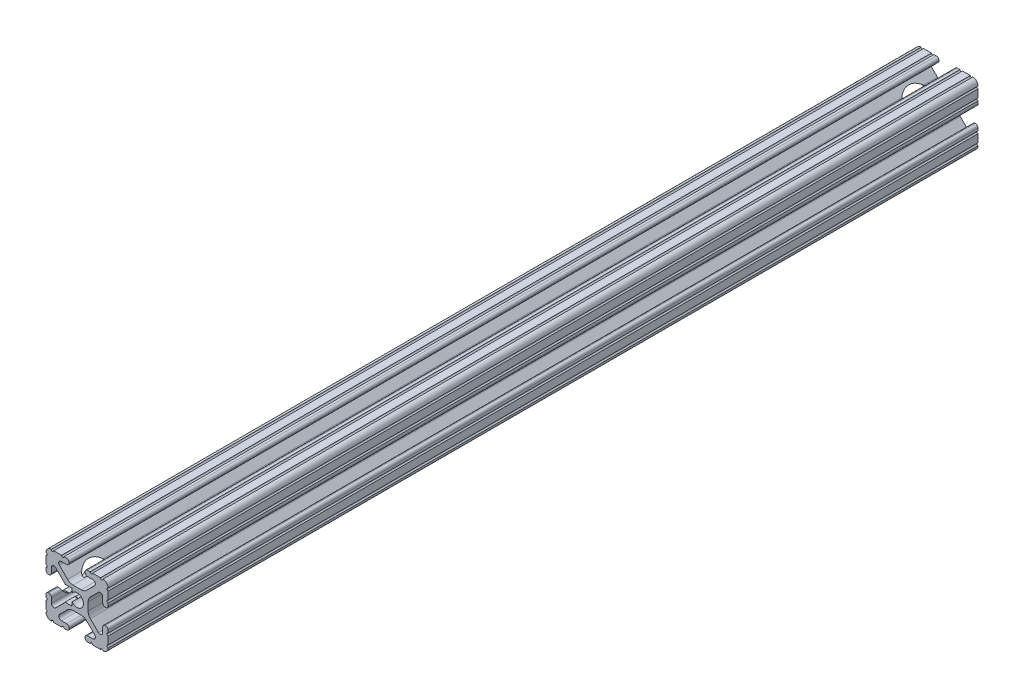
SolidWorks part; units mm, degrees
ref_plane "Front Plane" through (0, 0, 0) normal (0, 0, 1) x (1, 0, 0)
ref_plane "Top Plane" through (0, 0, 0) normal (0, 1, 0) x (1, 0, 0)
ref_plane "Right Plane" through (0, 0, 0) normal (1, 0, 0) x (0, 0, -1)
sketch "Sketch1" plane through (0, 0, 0) normal (0, 0, 1) x (1, 0, 0)
  line L88 (-7.1797, -8.6452) -> (-3.9523, -5.4237)
  line L89 (-1.7093, -4.4958) -> (1.7093, -4.4958)
  line L90 (3.9523, -5.4237) -> (7.1797, -8.6452)
  line L91 (6.4164, -10.4902) -> (4.2875, -10.4902)
  line L92 (3.2385, -11.5392) -> (3.2385, -11.651)
  line L93 (4.2875, -12.7) -> (5.3171, -12.7)
  line L94 (6.3331, -12.7) -> (9.5504, -12.7)
  line L95 (12.7, -9.5504) -> (12.7, -6.3331)
  line L96 (12.7, -5.3171) -> (12.7, -4.2875)
  line L97 (11.651, -3.2385) -> (11.5392, -3.2385)
  line L98 (10.4902, -4.2875) -> (10.4902, -6.4021)
  line L99 (8.7371, -7.1294) -> (5.441, -3.8408)
  line L100 (4.5085, -1.5932) -> (4.5085, 1.5932)
  line L101 (5.441, 3.8408) -> (8.7371, 7.1294)
  line L102 (10.4902, 6.4021) -> (10.4902, 4.2875)
  line L103 (11.5392, 3.2385) -> (11.651, 3.2385)
  line L104 (12.7, 4.2875) -> (12.7, 5.3171)
  line L105 (12.7, 6.3331) -> (12.7, 9.5504)
  line L106 (9.5504, 12.7) -> (6.3331, 12.7)
  line L107 (5.3171, 12.7) -> (4.2875, 12.7)
  line L108 (3.2385, 11.651) -> (3.2385, 11.5392)
  line L109 (4.2875, 10.4902) -> (6.4768, 10.4902)
  line L110 (7.207, 8.7244) -> (3.8983, 5.4232)
  line L111 (1.6558, 4.4958) -> (-1.6558, 4.4958)
  line L112 (-3.8983, 5.4232) -> (-7.207, 8.7244)
  line L113 (-6.4768, 10.4902) -> (-4.2875, 10.4902)
  line L114 (-3.2385, 11.5392) -> (-3.2385, 11.651)
  line L115 (-4.2875, 12.7) -> (-5.3171, 12.7)
  line L116 (-6.3331, 12.7) -> (-9.5504, 12.7)
  line L117 (-12.7, 9.5504) -> (-12.7, 6.3331)
  line L118 (-12.7, 5.3171) -> (-12.7, 4.2875)
  line L119 (-11.651, 3.2385) -> (-11.5392, 3.2385)
  line L120 (-10.4902, 4.2875) -> (-10.4902, 6.4021)
  line L121 (-8.7371, 7.1294) -> (-5.441, 3.8408)
  line L122 (-4.5085, 1.5932) -> (-4.5085, -1.5932)
  line L123 (-5.441, -3.8408) -> (-8.7371, -7.1294)
  line L124 (-10.4902, -6.4021) -> (-10.4902, -4.2875)
  line L125 (-11.5392, -3.2385) -> (-11.651, -3.2385)
  line L126 (-12.7, -4.2875) -> (-12.7, -5.3171)
  line L127 (-12.7, -6.3331) -> (-12.7, -9.5504)
  line L128 (-9.5504, -12.7) -> (-6.3331, -12.7)
  line L129 (-5.3171, -12.7) -> (-4.2875, -12.7)
  line L130 (-3.2385, -11.651) -> (-3.2385, -11.5392)
  line L131 (-4.2875, -10.4902) -> (-6.4164, -10.4902)
  circle A1 centre (0, 0) radius 2.6035
  arc A104 (-7.1797, -8.6452) -> (-6.4164, -10.4902) centre (-6.4164, -9.4098) ccw
  arc A105 (-1.7093, -4.4958) -> (-3.9523, -5.4237) centre (-1.7093, -7.6708) ccw
  arc A106 (3.9523, -5.4237) -> (1.7093, -4.4958) centre (1.7093, -7.6708) ccw
  arc A107 (6.4164, -10.4902) -> (7.1797, -8.6452) centre (6.4164, -9.4098) ccw
  arc A108 (4.2875, -10.4902) -> (3.2385, -11.5392) centre (4.2875, -11.5392) ccw
  arc A109 (3.2385, -11.651) -> (4.2875, -12.7) centre (4.2875, -11.651) ccw
  arc A110 (6.3331, -12.7) -> (5.3171, -12.7) centre (5.8251, -12.7) ccw
  arc A111 (10.5664, -12.6998) -> (9.5504, -12.7) centre (10.0584, -12.7) ccw
  arc A112 (10.5664, -12.6998) -> (12.6998, -10.5664) centre (10.5918, -10.5918) ccw
  arc A113 (12.7, -9.5504) -> (12.6998, -10.5664) centre (12.7, -10.0584) ccw
  arc A114 (12.7, -5.3171) -> (12.7, -6.3331) centre (12.7, -5.8251) ccw
  arc A115 (12.7, -4.2875) -> (11.651, -3.2385) centre (11.651, -4.2875) ccw
  arc A116 (11.5392, -3.2385) -> (10.4902, -4.2875) centre (11.5392, -4.2875) ccw
  arc A117 (8.7371, -7.1294) -> (10.4902, -6.4021) centre (9.4628, -6.4021) ccw
  arc A118 (4.5085, -1.5932) -> (5.441, -3.8408) centre (7.6835, -1.5932) ccw
  arc A119 (5.441, 3.8408) -> (4.5085, 1.5932) centre (7.6835, 1.5932) ccw
  arc A120 (10.4902, 6.4021) -> (8.7371, 7.1294) centre (9.4628, 6.4021) ccw
  arc A121 (10.4902, 4.2875) -> (11.5392, 3.2385) centre (11.5392, 4.2875) ccw
  arc A122 (11.651, 3.2385) -> (12.7, 4.2875) centre (11.651, 4.2875) ccw
  arc A123 (12.7, 6.3331) -> (12.7, 5.3171) centre (12.7, 5.8251) ccw
  arc A124 (12.6998, 10.5664) -> (12.7, 9.5504) centre (12.7, 10.0584) ccw
  arc A125 (12.6998, 10.5664) -> (10.5664, 12.6998) centre (10.5918, 10.5918) ccw
  arc A126 (9.5504, 12.7) -> (10.5664, 12.6998) centre (10.0584, 12.7) ccw
  arc A127 (5.3171, 12.7) -> (6.3331, 12.7) centre (5.8251, 12.7) ccw
  arc A128 (4.2875, 12.7) -> (3.2385, 11.651) centre (4.2875, 11.651) ccw
  arc A129 (3.2385, 11.5392) -> (4.2875, 10.4902) centre (4.2875, 11.5392) ccw
  arc A130 (7.207, 8.7244) -> (6.4768, 10.4902) centre (6.4768, 9.4563) ccw
  arc A131 (1.6558, 4.4958) -> (3.8983, 5.4232) centre (1.6558, 7.6708) ccw
  arc A132 (-3.8983, 5.4232) -> (-1.6558, 4.4958) centre (-1.6558, 7.6708) ccw
  arc A133 (-6.4768, 10.4902) -> (-7.207, 8.7244) centre (-6.4768, 9.4563) ccw
  arc A134 (-4.2875, 10.4902) -> (-3.2385, 11.5392) centre (-4.2875, 11.5392) ccw
  arc A135 (-3.2385, 11.651) -> (-4.2875, 12.7) centre (-4.2875, 11.651) ccw
  arc A136 (-6.3331, 12.7) -> (-5.3171, 12.7) centre (-5.8251, 12.7) ccw
  arc A137 (-10.5664, 12.6998) -> (-9.5504, 12.7) centre (-10.0584, 12.7) ccw
  arc A138 (-10.5664, 12.6998) -> (-12.6998, 10.5664) centre (-10.5918, 10.5918) ccw
  arc A139 (-12.7, 9.5504) -> (-12.6998, 10.5664) centre (-12.7, 10.0584) ccw
  arc A140 (-12.7, 5.3171) -> (-12.7, 6.3331) centre (-12.7, 5.8251) ccw
  arc A141 (-12.7, 4.2875) -> (-11.651, 3.2385) centre (-11.651, 4.2875) ccw
  arc A142 (-11.5392, 3.2385) -> (-10.4902, 4.2875) centre (-11.5392, 4.2875) ccw
  arc A143 (-8.7371, 7.1294) -> (-10.4902, 6.4021) centre (-9.4628, 6.4021) ccw
  arc A144 (-4.5085, 1.5932) -> (-5.441, 3.8408) centre (-7.6835, 1.5932) ccw
  arc A145 (-5.441, -3.8408) -> (-4.5085, -1.5932) centre (-7.6835, -1.5932) ccw
  arc A146 (-10.4902, -6.4021) -> (-8.7371, -7.1294) centre (-9.4628, -6.4021) ccw
  arc A147 (-10.4902, -4.2875) -> (-11.5392, -3.2385) centre (-11.5392, -4.2875) ccw
  arc A148 (-11.651, -3.2385) -> (-12.7, -4.2875) centre (-11.651, -4.2875) ccw
  arc A149 (-12.7, -6.3331) -> (-12.7, -5.3171) centre (-12.7, -5.8251) ccw
  arc A150 (-12.6998, -10.5664) -> (-12.7, -9.5504) centre (-12.7, -10.0584) ccw
  arc A151 (-12.6998, -10.5664) -> (-10.5664, -12.6998) centre (-10.5918, -10.5918) ccw
  arc A152 (-9.5504, -12.7) -> (-10.5664, -12.6998) centre (-10.0584, -12.7) ccw
  arc A153 (-5.3171, -12.7) -> (-6.3331, -12.7) centre (-5.8251, -12.7) ccw
  arc A154 (-4.2875, -12.7) -> (-3.2385, -11.651) centre (-4.2875, -11.651) ccw
  arc A155 (-3.2385, -11.5392) -> (-4.2875, -10.4902) centre (-4.2875, -11.5392) ccw
extrude "Boss-Extrude1" add sketch "Sketch1" along normal mid plane 355.6
ref_plane "Plane1" through (0, 0, 0) normal (0, 1, 0) x (1, 0, 0)
ref_plane "Plane2" through (0, 0, 0) normal (-1, 0, 0) x (0, 0, 1)
sketch "Sketch2" plane through (-12.7, 0, 0) normal (-1, 0, 0) x (0, 0, 1)
  line L0 (177.8, -6.3331) -> (177.8, -9.5504) construction
  line L1 (177.8, -6.3331) -> (177.8, -9.5504) construction
  line L2 (177.8, 12.7) -> (-177.8, 12.7) construction
  line L3 (177.8, -12.7) -> (-177.8, -12.7) construction
  line L4 (177.8, 12.7) -> (-177.8, 12.7) construction
  line L5 (177.8, -12.7) -> (-177.8, -12.7) construction
  line L6 (137.5638, -12.7) -> (137.5638, 12.7) construction
  line L7 (226.3476, 0) -> (105.4883, 0) construction
  line L9 (177.8, 3.175) -> (167.64, 3.175)
  line L10 (177.8, 3.175) -> (177.8, -3.175)
  line L11 (177.8, -3.175) -> (167.64, -3.175)
  line L12 (167.64, 3.175) -> (167.64, -3.175)
  line L13 (177.8, 3.175) -> (167.64, -3.175) construction
  line L14 (177.8, -3.175) -> (167.64, 3.175) construction
  circle A0 centre (167.64, 0) radius 6.985
  point P11 (172.72, 0)
  point P18 (167.6652, 0)
  line M10 (177.8, -6.3331) -> (-177.8, -6.3331)
  dimension "D1" = 13.97
  dimension "D2" = 6.35
  dimension "D3" = 10.16
extrude "Cut-Extrude1" cut sketch "Sketch2" against normal blind 10.668 contours L11 A0 L9 L12 | A0 L11 L10 L9 | A0 L11 L12 L9 M10 region at (-12.7, 0, 176.0808) region at (-12.7, 0, 171.012) region at (-12.7, 0.158, 166.3034)
mirror "Mirror1" about plane through (0, 0, 0) normal (0, 0, 1) of "Cut-Extrude1"
